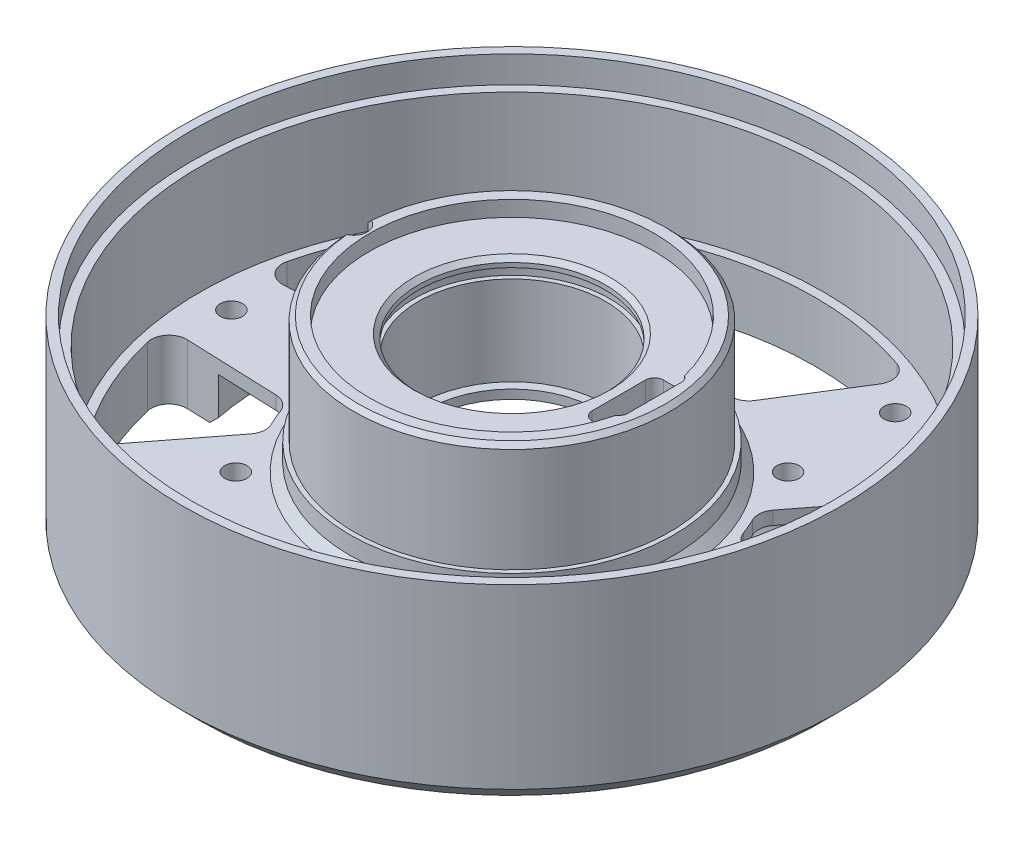
SolidWorks part; units mm, degrees
ref_plane "Front Plane" through (0, 0, 0) normal (0, 0, 1) x (1, 0, 0)
ref_plane "Top Plane" through (0, 0, 0) normal (0, 1, 0) x (1, 0, 0)
ref_plane "Right Plane" through (0, 0, 0) normal (1, 0, 0) x (0, 0, -1)
ref_axis "Axis1" through (0, 0, 0) along (0, 1, 0)
sketch "Sketch1" plane through (0, 0, 0) normal (0, 0, 1) x (1, 0, 0)
  line L0 (0, 0) -> (0, -50277.2651) construction
  line L1 (-17.7, 6) -> (-17.7, -6.2)
  line L2 (-17.7, -6.2) -> (-18.2, -6.2)
  line L3 (-18.2, -6.2) -> (-18.2, -8.2)
  line L4 (-19.2, -9.2) -> (-35, -9.2)
  line L7 (-35, -9.2) -> (-35, 3)
  line L8 (-35, 3) -> (-36, 3)
  line L9 (-36, 3) -> (-36, 6)
  line L10 (-36, 6) -> (-37, 6)
  line L11 (-37, 6) -> (-37, -13.9)
  line L12 (-35, -15.9) -> (-28, -15.9)
  line L13 (-28, -15.9) -> (-28, -10.7)
  line L14 (-28, -10.7) -> (-16.7, -10.7)
  line L23 (-16, 4.25) -> (-16, 6)
  line L24 (-16, 6) -> (-17.7, 6)
  line L26 (19.25, 6) -> (-19.25, 6) construction
  line L27 (-34, 8) -> (-34, -6) construction
  line L28 (-19.25, -6) -> (19.25, -6) construction
  line L31 (-16, 4.25) -> (-10.5, 4.25)
  line L32 (11.5, -15.9) -> (-11.5, -15.9) construction
  line L37 (-16.7, -10.7) -> (-16.7, -8.85)
  line L38 (-16.7, -8.85) -> (-9.5, -8.85)
  line L39 (-9.5, -8.85) -> (-9.5, -7.85)
  line L40 (-9.5, -7.85) -> (-10.5, -7.85)
  line L42 (-37, -13.9) -> (-35, -15.9)
  line L44 (-18.2, -8.2) -> (-19.2, -9.2)
  line L45 (-10.5, 4.25) -> (-10.5, 3.25)
  line L47 (-10.5, 3.25) -> (-11, 3.25)
  line L48 (-11, 3.25) -> (-11, 2.15)
  line L49 (-11, 2.15) -> (-10.5, 2.15)
  line L50 (-10.5, 2.15) -> (-10.5, -7.85)
  line L51 (8.9533, 2.15) -> (-8.9533, 2.15) construction
  line L52 (-8.9533, -7.85) -> (8.9533, -7.85) construction
  point P6 (-18.2, -9.2)
  point P15 (-37, -15.9)
  point P31 (-31.5, -15.9)
  dimension "D1" = 35.4
  dimension "D2" = 32
  dimension "D3" = 0.5
  dimension "D4" = 3
  dimension "D5" = 1
  dimension "D6" = 1.5
  dimension "D7" = 0.2
  dimension "D8" = 2
  dimension "D9" = 3
  dimension "D10" = 72
  dimension "D11" = 1.5
  dimension "D12" = 0.5
  dimension "D13" = 63
  dimension "D14" = 1.1
  dimension "D15" = 21
  dimension "D17" = 1
  dimension "D18" = 1
  dimension "D19" = 1
revolve "Revolve1" add sketch "Sketch1" angle 360 about L0
sketch "Sketch2" plane through (0, 0, 0) normal (0, 1, 0) x (1, 0, 0)
  circle A0 centre (-17.75, 0) radius 1.5
  dimension "D1" = 3
extrude "Cut-Extrude2" cut sketch "Sketch2" along normal up to next and the other way up to surface other way up to face at (0, -6.2, 18.2)
sketch "Sketch3" plane through (0, 0, 0) normal (0, 1, 0) x (1, 0, 0)
  circle A0 centre (-15.5, -15.5) radius 3.5
  circle A1 centre (15.5, -15.5) radius 3.5
  circle A2 centre (15.5, 15.5) radius 3.5
  circle A3 centre (-15.5, 15.5) radius 3.5
  dimension "D1" = 7
extrude "Boss-Extrude1" add sketch "Sketch3" against normal up to surface (4 mm away) from surface starting at face at (0, -10.7, 16.7)
hole_wizard "M3x0.5 Tapped Hole1" positions "Sketch4" profile "Sketch6" tap size "M3x0.5" standard "ANSI Metric" end condition through all
sketch "Sketch4" plane through (0, -14.7, 0) normal (0, -1, 0) x (-1, 0, 0)
  point P0 (-15.5, 15.5)
  point P3 (15.5, 15.5)
  point P6 (15.5, -15.5)
  point P9 (-15.5, -15.5)
sketch "Sketch6" plane through (15.5, -14.7, -15.5) normal (1, 0, 0) x (0, 0, -1)
  line L0 (0, 0) -> (0, 20.7)
  line L1 (0, 20.7) -> (1.25, 20.7)
  line L2 (1.25, 20.7) -> (1.25, 0.35)
  line L3 (1.25, 0.35) -> (1.6, 0)
  line L5 (1.6, 0) -> (0, 0)
  line L6 (-1.25, 0.35) -> (-1.6, 0) construction
  line L11 (0, -6.35) -> (0, 107.95) construction
  dimension "Thru Tap Drill Dia." = 2.5
  dimension "Thru Tap Drill Depth" = 20.7
  dimension "Near C'Sink Dia." = 3.2
  dimension "Near C'Sink Angle" = 90
cosmetic thread "Hole Thread5" parameters "D2"=3
cosmetic thread "Hole Thread6" parameters "D2"=3
cosmetic thread "Hole Thread7" parameters "D2"=3
cosmetic thread "Hole Thread8" parameters "D2"=3
sketch "Sketch7" plane through (0, 0, 0) normal (0, 1, 0) x (1, 0, 0)
  line L0 (-4.2, 18.5) -> (1.8, 12.5) construction
  line L1 (-4.2, 12) -> (1.8, 12)
  line L2 (-4.7, 12.5) -> (-4.7, 18.5)
  line L3 (-4.2, 19) -> (1.8, 19)
  line L4 (2.3, 12.5) -> (2.3, 18.5)
  arc A0 (1.8, 12) -> (2.3, 12.5) centre (1.8, 12.5) ccw
  arc A1 (-4.7, 18.5) -> (-4.2, 19) centre (-4.2, 18.5) cw
  arc A2 (1.8, 19) -> (2.3, 18.5) centre (1.8, 18.5) cw
  arc A3 (-4.2, 12) -> (-4.7, 12.5) centre (-4.2, 12.5) cw
  point P12 (-1.2, 15.5)
  dimension "D1" = 0.5
  dimension "D2" = 15.5
  dimension "D3" = 1.2
  dimension "D4" = 7
  dimension "D5" = 7
extrude "Boss-Extrude2" add sketch "Sketch7" against normal offset from surface (4.35 mm away) 1.5 from surface starting at face at (0, -8.85, 9.5)
sketch "Sketch9" plane through (0, 0, 0) normal (0, 1, 0) x (1, 0, 0)
  circle A0 centre (0, 0) radius 23.1 construction
  circle A2 centre (0, -23.1) radius 4.9
  circle A5 centre (0, 23.1) radius 4.9
  circle A6 centre (0, 0) radius 28 construction
  circle A7 centre (0, 0) radius 18.2 construction
extrude "Cut-Extrude4" [suppressed] cut sketch "Sketch9" against normal through all
sketch "Sketch10" plane through (0, 0, 0) normal (0, 1, 0) x (1, 0, 0)
  line L1 (13, 4) -> (15, 4)
  line L2 (12, 3) -> (12, -3)
  line L3 (13, -4) -> (15, -4)
  line L4 (16, 3) -> (16, -3)
  line L5 (12, 4) -> (16, -4) construction
  line L6 (12, -4) -> (16, 4) construction
  arc A0 (15, -4) -> (16, -3) centre (15, -3) ccw
  arc A1 (15, 4) -> (16, 3) centre (15, 3) cw
  arc A2 (12, -3) -> (13, -4) centre (13, -3) ccw
  arc A3 (13, 4) -> (12, 3) centre (13, 3) ccw
  point P0 (14, 0)
  point P19 (10.5, 0)
  dimension "D1" = 1
  dimension "D2" = 1.5
  dimension "D3" = 4
  dimension "D4" = 8
extrude "Cut-Extrude5" cut sketch "Sketch10" against normal through all both and the other way through all
chamfer "Chamfer1" distance 0.5 angle 45 2 edges at (17.7, 6, 0) (0, 4.25, 10.5)
hole_wizard "M3x0.5 Tapped Hole2" positions "Sketch11" profile "Sketch12" tap size "M3x0.5" standard "ANSI Metric" end condition through all
sketch "Sketch11" plane through (0, -15.9, 0) normal (0, -1, 0) x (-1, 0, 0)
  circle A0 centre (0, 0) radius 31.5 construction
  point P0 (-31.5, 0)
  dimension "D2" = 63
sketch "Sketch12" plane through (31.5, -15.9, 0) normal (1, 0, 0) x (0, 0, -1)
  line L0 (0, 0) -> (0, 21.9)
  line L1 (0, 21.9) -> (1.25, 21.9)
  line L2 (1.25, 21.9) -> (1.25, 0.35)
  line L3 (1.25, 0.35) -> (1.6, 0)
  line L5 (1.6, 0) -> (0, 0)
  line L6 (-1.25, 0.35) -> (-1.6, 0) construction
  line L11 (0, -6.35) -> (0, 107.95) construction
  dimension "Thru Tap Drill Dia." = 2.5
  dimension "Thru Tap Drill Depth" = 21.9
  dimension "Near C'Sink Dia." = 3.2
  dimension "Near C'Sink Angle" = 90
cosmetic thread "Hole Thread12" parameters "D2"=3
pattern_circular "CirPattern2" count 6 over 360 about axis through (0, 0, 0) along (0, 1, 0) of "M3x0.5 Tapped Hole2"
sketch "Sketch13" plane through (0, 0, 0) normal (0, 1, 0) x (1, 0, 0)
  line L0 (0, 0) -> (-50000, 0) construction
  line L1 (0, 0) -> (0, 50000) construction
  line L4 (-12.0934, 29.1985) -> (-6.6703, 20.5706)
  line L6 (12.0934, 29.1985) -> (6.6703, 20.5706)
  line L7 (12.0934, -29.1985) -> (6.6703, -20.5706)
  line L8 (-12.0934, -29.1985) -> (-6.6703, -20.5706)
  line L17 (18.3678, 10.9609) -> (24.8178, 19.3068)
  line L18 (31.0664, 5.3608) -> (20.7268, 5.7533)
  line L19 (31.0664, -5.3608) -> (20.7268, -5.7533)
  line L20 (18.3678, -10.9609) -> (24.8178, -19.3068)
  line L21 (-18.3678, -10.9609) -> (-24.8178, -19.3068)
  line L22 (-31.0664, -5.3608) -> (-20.7268, -5.7533)
  line L23 (-31.0664, 5.3608) -> (-20.7268, 5.7533)
  line L24 (-18.3678, 10.9609) -> (-24.8178, 19.3068)
  arc A0 (-11.0501, 32.1542) -> (11.0501, 32.1542) centre (0, 0) cw
  arc A5 (-4.5286, 19.6858) -> (4.5286, 19.6858) centre (0, 0) cw
  circle A10 centre (0, 0) radius 19.2 construction
  circle A16 centre (0, 0) radius 35 construction
  arc A17 (-4.5286, -19.6858) -> (4.5286, -19.6858) centre (0, 0) ccw
  arc A18 (-11.0501, -32.1542) -> (11.0501, -32.1542) centre (0, 0) ccw
  arc A27 (18.153, 8.8606) -> (18.9285, 7.0535) centre (0, 0) cw
  arc A28 (28.0503, 19.2141) -> (33.0887, 7.8193) centre (0, 0) cw
  arc A29 (28.0503, -19.2141) -> (33.0887, -7.8193) centre (0, 0) ccw
  arc A30 (18.153, -8.8606) -> (18.9285, -7.0535) centre (0, 0) ccw
  arc A31 (-18.153, -8.8606) -> (-18.9285, -7.0535) centre (0, 0) cw
  arc A32 (-28.0503, -19.2141) -> (-33.0887, -7.8193) centre (0, 0) cw
  arc A33 (-28.0503, 19.2141) -> (-33.0887, 7.8193) centre (0, 0) ccw
  arc A34 (-18.153, 8.8606) -> (-18.9285, 7.0535) centre (0, 0) ccw
  arc A35 (-18.9285, 7.0535) -> (-20.7268, 5.7533) centre (-20.8026, 7.7518) cw
  arc A36 (-18.153, 8.8606) -> (-18.3678, 10.9609) centre (-19.9503, 9.7379) ccw
  arc A37 (-33.0887, 7.8193) -> (-31.0664, 5.3608) centre (-31.1423, 7.3593) ccw
  arc A38 (-28.0503, 19.2141) -> (-24.8178, 19.3068) centre (-26.4003, 18.0838) cw
  arc A39 (-33.0887, -7.8193) -> (-31.0664, -5.3608) centre (-31.1423, -7.3593) cw
  arc A40 (-28.0503, -19.2141) -> (-24.8178, -19.3068) centre (-26.4003, -18.0838) ccw
  arc A41 (-18.9285, -7.0535) -> (-20.7268, -5.7533) centre (-20.8026, -7.7518) ccw
  arc A42 (-18.153, -8.8606) -> (-18.3678, -10.9609) centre (-19.9503, -9.7379) cw
  arc A43 (18.9285, -7.0535) -> (20.7268, -5.7533) centre (20.8026, -7.7518) cw
  arc A44 (18.153, -8.8606) -> (18.3678, -10.9609) centre (19.9503, -9.7379) ccw
  arc A45 (33.0887, -7.8193) -> (31.0664, -5.3608) centre (31.1423, -7.3593) ccw
  arc A46 (28.0503, -19.2141) -> (24.8178, -19.3068) centre (26.4003, -18.0838) cw
  arc A47 (33.0887, 7.8193) -> (31.0664, 5.3608) centre (31.1423, 7.3593) cw
  arc A48 (28.0503, 19.2141) -> (24.8178, 19.3068) centre (26.4003, 18.0838) ccw
  arc A49 (11.0501, -32.1542) -> (12.0934, -29.1985) centre (10.4001, -30.2628) ccw
  arc A50 (-11.0501, -32.1542) -> (-12.0934, -29.1985) centre (-10.4001, -30.2628) cw
  arc A51 (4.5286, -19.6858) -> (6.6703, -20.5706) centre (4.977, -21.6349) cw
  arc A52 (-4.5286, -19.6858) -> (-6.6703, -20.5706) centre (-4.977, -21.6349) ccw
  arc A53 (18.9285, 7.0535) -> (20.7268, 5.7533) centre (20.8026, 7.7518) ccw
  arc A54 (4.5286, 19.6858) -> (6.6703, 20.5706) centre (4.977, 21.6349) ccw
  arc A55 (-4.5286, 19.6858) -> (-6.6703, 20.5706) centre (-4.977, 21.6349) cw
  arc A56 (11.0501, 32.1542) -> (12.0934, 29.1985) centre (10.4001, 30.2628) cw
  arc A57 (18.153, 8.8606) -> (18.3678, 10.9609) centre (19.9503, 9.7379) cw
  arc A58 (-11.0501, 32.1542) -> (-12.0934, 29.1985) centre (-10.4001, 30.2628) ccw
  point P9 (0, 20.2)
  point P10 (0, 34)
  point P50 (-19.3477, 5.8056)
  point P53 (-17.5825, 9.9447)
  point P56 (-33.5899, 5.265)
  point P59 (-26.4281, 21.3905)
  point P62 (-33.5899, -5.265)
  point P65 (-26.4281, -21.3905)
  point P68 (-19.3477, -5.8056)
  point P71 (-17.5825, -9.9447)
  point P74 (19.3477, -5.8056)
  point P77 (17.5825, -9.9447)
  point P80 (33.5899, -5.265)
  point P83 (26.4281, -21.3905)
  point P86 (33.5899, 5.265)
  point P89 (26.4281, 21.3905)
  point P92 (13.3855, -31.2542)
  point P95 (-13.3855, -31.2542)
  point P98 (5.8863, -19.3233)
  point P101 (-5.8863, -19.3233)
  point P104 (19.3477, 5.8056)
  point P107 (5.8863, 19.3233)
  point P110 (-5.8863, 19.3233)
  point P113 (13.3855, 31.2542)
  point P116 (17.5825, 9.9447)
  point P119 (-13.3855, 31.2542)
  dimension "D1" = 1
  dimension "D2" = 1
  dimension "D3" = 2
extrude "Cut-Extrude6" cut sketch "Sketch13" against normal through all
fillet "Fillet1" radius 2 2 edges at (2.3, -9.775, -16.5409) (-4.7, -9.775, -16.025)
sketch "Sketch14" plane through (0, 0, 0) normal (0, 1, 0) x (1, 0, 0)
  line L0 (0, 0) -> (14, 0) construction
  line L1 (16, 3) -> (16, -3) construction
  line L6 (13, -7.5) -> (15, -7.5)
  line L7 (12, -6.5) -> (12, 6.5)
  line L8 (13, 7.5) -> (15, 7.5)
  line L9 (16, -6.5) -> (16, 6.5)
  line L10 (12, -7.5) -> (16, 7.5) construction
  line L11 (12, 7.5) -> (16, -7.5) construction
  line L12 (12, 3) -> (12, -3) construction
  arc A7 (15, -7.5) -> (16, -6.5) centre (15, -6.5) ccw
  arc A8 (12, 6.5) -> (13, 7.5) centre (13, 6.5) cw
  arc A9 (13, -7.5) -> (12, -6.5) centre (13, -6.5) cw
  arc A10 (15, 7.5) -> (16, 6.5) centre (15, 6.5) cw
  dimension "D1" = 1
  dimension "D2" = 13
extrude "Cut-Extrude7" cut sketch "Sketch14" along normal offset from surface 11.38 and the other way through all from surface up to face at (7.9374, 6, 0) starting at face at (14, -8.85, 0)
sketch "Sketch15" plane through (0, -10.7, 0) normal (0, -1, 0) x (1, 0, 0)
  line L1 (16, 4.7843) -> (16, -4.7843)
  line L2 (16, 4.7843) -> (16, -4.7843)
  arc A1 (16, -4.7843) -> (16, 4.7843) centre (0, 0) ccw
  arc A2 (16, -4.7843) -> (16, 4.7843) centre (0, 0) ccw
  dimension "D1" = 0
extrude "Boss-Extrude3" add sketch "Sketch15" against normal up to surface (1.85 mm away) up to face at (16.35, -8.85, 0)
chamfer "Chamfer2" distance 1 angle 45 6 edges at (28, -15.9, 0) (17.0802, -15.9, 22.1871) (-17.0802, -15.9, 22.1871) (-28, -15.9, 0) (-17.0802, -15.9, -22.1871) (17.0802, -15.9, -22.1871)
